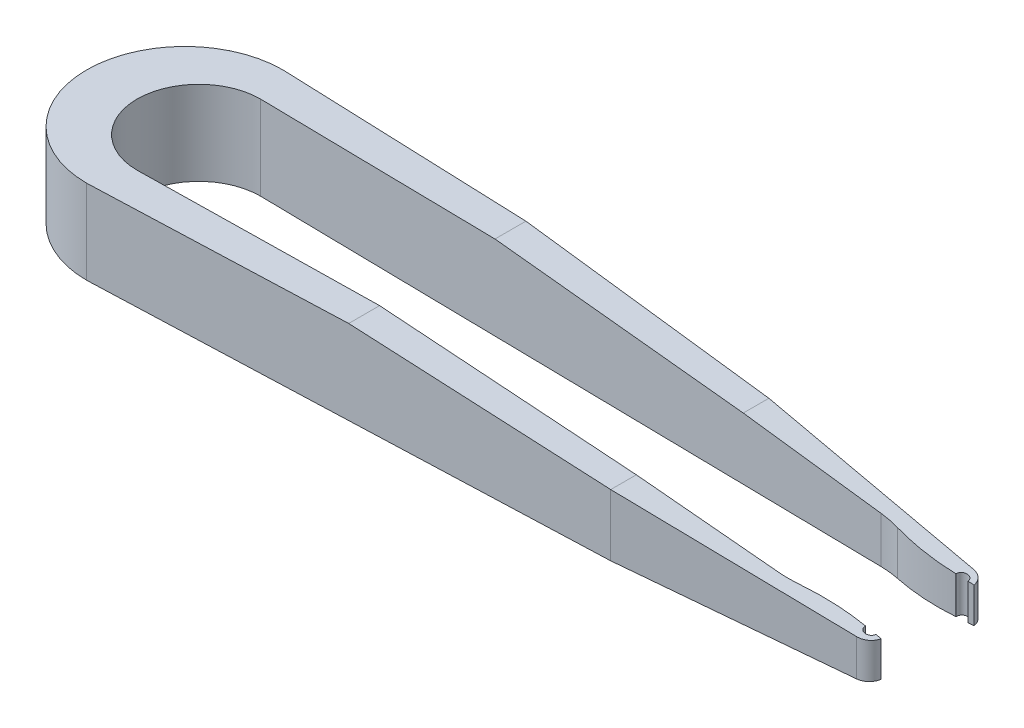
SolidWorks part; units mm, degrees
ref_plane "Front Plane" through (0, 0, 0) normal (0, 0, 1) x (1, 0, 0)
ref_plane "Top Plane" through (0, 0, 0) normal (0, 1, 0) x (1, 0, 0)
ref_plane "Right Plane" through (0, 0, 0) normal (1, 0, 0) x (0, 0, -1)
sketch "Sketch1" plane through (0, 0, 0) normal (0, 1, 0) x (1, 0, 0)
  line L1 (-38.1, -8.89) -> (38.1, -8.89)
  line L2 (-38.1, -8.89) -> (-38.1, 8.89)
  line L3 (-38.1, 8.89) -> (38.1, 8.89)
  line L4 (38.1, -8.89) -> (38.1, 8.89)
  line L5 (-38.1, -8.89) -> (38.1, 8.89) construction
  line L6 (-38.1, 8.89) -> (38.1, -8.89) construction
  point P0 (0, 0)
extrude "Boss-Extrude1" add sketch "Sketch1" along normal blind 7.62
sketch "Sketch2" plane through (0, 7.62, 0) normal (0, 1, 0) x (1, 0, 0)
  line L0 (38.1, -8.89) -> (38.1, 8.89) construction
  line L1 (107.95, 3.81) -> (-31.75, 3.81)
  line L2 (107.95, 3.81) -> (107.95, -3.81)
  line L3 (107.95, -3.81) -> (-31.75, -3.81)
  line L4 (-31.75, 3.81) -> (-31.75, -3.81)
  line L5 (107.95, 3.81) -> (-31.75, -3.81) construction
  line L6 (107.95, -3.81) -> (-31.75, 3.81) construction
  line L7 (-27.94, 5.588) -> (32.8354, 4.572)
  line L8 (32.8354, 4.572) -> (32.8354, 0.2872)
  line L9 (32.8354, 0.2872) -> (32.8354, -4.572)
  line L10 (-27.94, 0) -> (-27.94, -5.588)
  line L11 (32.8354, -4.572) -> (-27.94, -5.588)
  line L12 (-55, 0) -> (55, 0) construction
  circle A1 centre (-27.94, 0) radius 5.588
  point P0 (38.1, 0)
  dimension "D1" = 66.04
  dimension "D2" = 4.572
  dimension "D3" = 4.572
fillet "Fillet1" radius 8.89 2 edges at (-38.1, 3.81, -8.89) (-38.1, 3.81, 8.89)
extrude "Cut-Extrude8" cut sketch "Sketch2" against normal through all
sketch "Sketch8" plane through (0, 7.62, 0) normal (0, 1, 0) x (1, 0, 0)
  line L0 (-29.21, 8.89) -> (38.1, 6.35)
  line L1 (38.1, 3.81) -> (38.1, 8.89) construction
  line L2 (38.1, 6.35) -> (38.1, 8.89)
  line L3 (38.1, 8.89) -> (-29.21, 8.89)
extrude "Cut-Extrude9" cut sketch "Sketch8" against normal through all
mirror "Mirror5" about plane through (0, 0, 0) normal (0, 0, 1) of "Cut-Extrude9"
sketch "Sketch9" plane through (0, 7.62, 0) normal (0, 1, 0) x (1, 0, 0)
  line L0 (16.5434, 7.1635) -> (38.1, 5.1851)
  line L1 (-29.21, 8.89) -> (38.1, 6.35) construction
  line L2 (38.1, 3.81) -> (38.1, 6.35) construction
  line L3 (38.1, 5.1851) -> (38.1, 6.35)
  line L4 (38.1, 6.35) -> (16.5434, 7.1635)
extrude "Cut-Extrude10" cut sketch "Sketch9" against normal through all
mirror "Mirror6" about plane through (0, 0, 0) normal (0, 0, 1) of "Cut-Extrude10"
fillet "Fillet5" radius 8.89 2 edges at (32.8354, 3.81, 4.572) (32.8354, 3.81, -4.572)
fillet "Fillet6" radius 1.27 2 edges at (38.1, 3.81, 5.1851) (38.1, 3.81, -5.1851)
sketch "Sketch10" plane through (0, 7.62, 0) normal (0, 1, 0) x (1, 0, 0)
  line L0 (32.8354, 3.81) -> (38.0867, 4.2097)
  line L1 (38.0867, 4.2097) -> (38.7378, 3.81)
  line L2 (38.7378, 3.81) -> (32.8354, 3.81)
  arc A0 (38.1, 4.0263) -> (36.9461, 5.291) centre (36.83, 4.0263) ccw construction
extrude "Cut-Extrude11" cut sketch "Sketch10" against normal through all
mirror "Mirror7" about plane through (0, 0, 0) normal (0, 0, 1) of "Cut-Extrude11"
sketch "Sketch11" plane through (0, 7.62, 0) normal (0, 1, 0) x (1, 0, 0)
  line L0 (38.0867, 4.2097) -> (32.8354, 3.81) construction
  circle A0 centre (37.0707, 4.1324) radius 0.508
  dimension "D1" = 1.016
extrude "Cut-Extrude12" cut sketch "Sketch11" against normal through all
mirror "Mirror8" about plane through (0, 0, 0) normal (0, 0, 1) of "Cut-Extrude12"
sketch "Sketch13" plane through (0, 0, 0) normal (0, 0, 1) x (1, 0, 0)
  line L0 (-6.3333, 7.62) -> (16.5434, 5.5949)
  line L1 (-29.21, 7.62) -> (16.5434, 7.62) construction
  line L2 (16.5434, 0) -> (16.5434, 7.62) construction
  line L3 (16.5434, 5.5949) -> (38.0867, 3.1945)
  line L4 (38.0867, 0) -> (38.0867, 7.62) construction
  line L5 (38.0867, 3.1945) -> (38.0867, 7.62)
  line L6 (38.0867, 7.62) -> (-6.3333, 7.62)
extrude "Cut-Extrude14" cut sketch "Sketch13" against normal through all and the other way through all
fillet "Fillet7" radius 20.32 2 edges at (32.8354, 1.8898, -3.81) (32.8354, 1.8898, 3.81)
